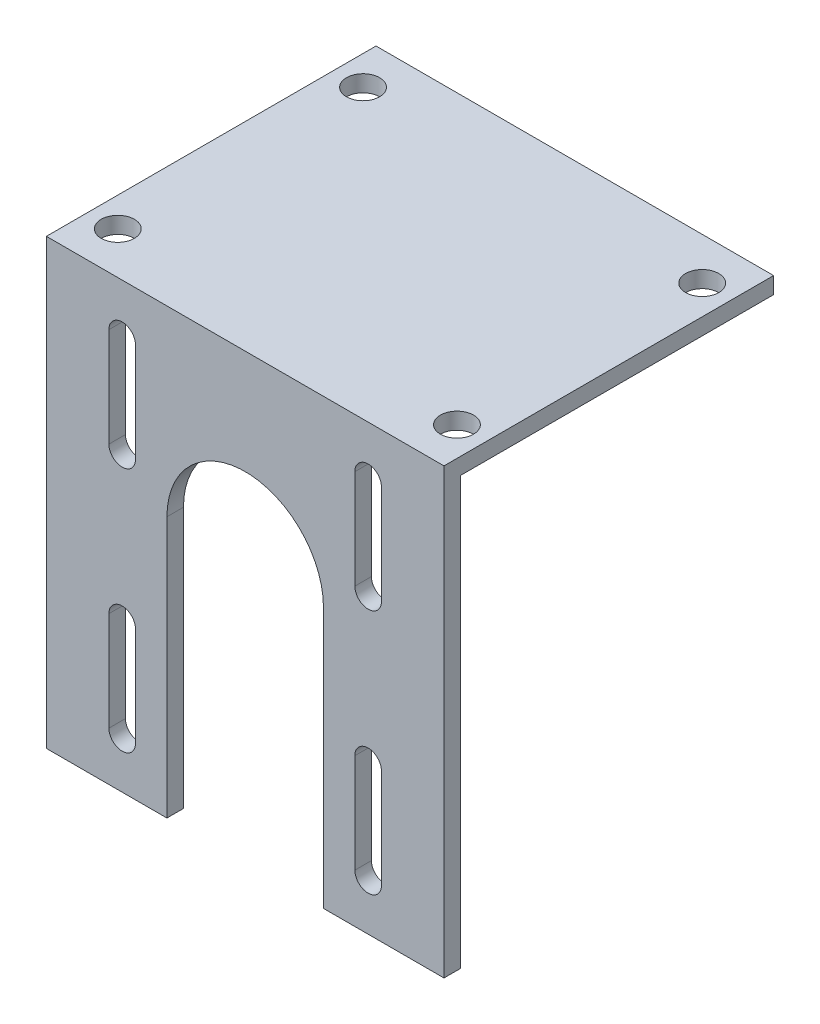
SolidWorks part; units mm, degrees
material "6061 Alloy"
ref_plane "Front Plane" through (0, 0, 0) normal (0, 0, 1) x (1, 0, 0)
ref_plane "Top Plane" through (0, 0, 0) normal (0, 1, 0) x (1, 0, 0)
ref_plane "Right Plane" through (0, 0, 0) normal (1, 0, 0) x (0, 0, -1)
sketch "Sketch1" plane through (0, 0, 0) normal (0, 0, 1) x (1, 0, 0)
  line L2 (0, 0) -> (0, -100)
  line L3 (0, -100) -> (76.2, -100)
  line L9 (76.2, -100) -> (76.2, 0)
  line L10 (0, 0) -> (76.2, 0)
  line L11 (14.53, -19) -> (61.67, -19) construction
  line L12 (38.1, 0) -> (38.1, -100) construction
  line L14 (14.53, -9.5) -> (14.53, -28.5) construction
  line L15 (61.67, -47.5975) -> (61.67, -19) construction
  line L16 (17.08, -9.5) -> (17.08, -28.5)
  line L17 (11.98, -9.5) -> (11.98, -28.5)
  line L18 (61.67, -9.5) -> (61.67, -28.5) construction
  line L19 (59.12, -9.5) -> (59.12, -28.5)
  line L20 (64.22, -9.5) -> (64.22, -28.5)
  line L21 (14.53, -75.64) -> (14.53, -56.64) construction
  line L22 (17.08, -75.64) -> (17.08, -56.64)
  line L23 (11.98, -75.64) -> (11.98, -56.64)
  line L24 (61.67, -75.64) -> (61.67, -56.64) construction
  line L25 (59.12, -75.64) -> (59.12, -56.64)
  line L26 (64.22, -75.64) -> (64.22, -56.64)
  arc A8 (17.08, -9.5) -> (11.98, -9.5) centre (14.53, -9.5) ccw
  arc A9 (11.98, -28.5) -> (17.08, -28.5) centre (14.53, -28.5) ccw
  arc A10 (59.12, -9.5) -> (64.22, -9.5) centre (61.67, -9.5) cw
  arc A11 (64.22, -28.5) -> (59.12, -28.5) centre (61.67, -28.5) cw
  arc A12 (17.08, -75.64) -> (11.98, -75.64) centre (14.53, -75.64) cw
  arc A13 (11.98, -56.64) -> (17.08, -56.64) centre (14.53, -56.64) cw
  arc A14 (59.12, -75.64) -> (64.22, -75.64) centre (61.67, -75.64) ccw
  arc A15 (64.22, -56.64) -> (59.12, -56.64) centre (61.67, -56.64) ccw
  point P10 (16.7578, -17.7303)
  point P11 (0, 0)
  point P12 (63.57, -68.5233)
  point P14 (0, 0)
  point P15 (0, 0)
  point P16 (38.1, -19)
  point P20 (14.53, -19)
  point P21 (76.2, -100)
  point P26 (0, 0)
  point P29 (76.2, 0)
  point P31 (61.67, -19)
  point P37 (14.53, -66.14)
  point P44 (61.67, -66.14)
  dimension "D3" = 47.14
  dimension "D4" = 47.14
  dimension "D6" = 19
  dimension "D5" = 2.55
  dimension "D1" = 76.2
  dimension "D2" = 100
  dimension "D7" = 19
  dimension "D8" = 19
  dimension "D9" = 19
extrude "Boss-Extrude1" add sketch "Sketch1" along normal blind 3.175
sketch "Sketch2" plane through (0, 0, 3.175) normal (0, 0, 1) x (1, 0, 0)
  line L0 (23.1, -35) -> (23.1, -100)
  line L1 (0, -100) -> (76.2, -100) construction
  line L2 (53.1, -35) -> (53.1, -100)
  line L3 (76.2, 0) -> (0, 0) construction
  line L8 (23.1, -100) -> (53.1, -100)
  arc A3 (23.1, -35) -> (53.1, -35) centre (38.1, -35) cw
  point P4 (38.1, 0)
  dimension "D1" = 15
  dimension "D2" = 35
extrude "Cut-Extrude2" cut sketch "Sketch2" against normal up to next
sketch "Sketch4" plane through (0, 0, 0) normal (0, 0, -1) x (-1, 0, 0)
  line L0 (0, 0) -> (0, -100) construction
  line L1 (-76.2, 0) -> (0, 0)
  line L2 (-76.2, 0) -> (-76.2, -3.175)
  line L3 (-76.2, -3.175) -> (0, -3.175)
  line L4 (0, 0) -> (0, -3.175)
  dimension "D1" = 3.175
extrude "Boss-Extrude2" add sketch "Sketch4" along normal blind 60
sketch "Sketch5" plane through (0, 0, 0) normal (0, 1, 0) x (1, 0, 0)
  line L2 (5.6, 51.9125) -> (70.6, 51.9125) construction
  line L3 (70.6, 51.9125) -> (70.6, 4.9125) construction
  line L4 (70.6, 4.9125) -> (5.6, 4.9125) construction
  line L5 (5.6, 4.9125) -> (5.6, 51.9125) construction
  line L6 (38.1, -940) -> (38.1, 49060) construction
  line L7 (0, 60) -> (76.2, 60) construction
  line L8 (-1000, 28.4125) -> (49000, 28.4125) construction
  line L9 (0, -3.175) -> (0, 60) construction
  circle A0 centre (5.6, 51.9125) radius 3.175
  circle A1 centre (5.6, 4.9125) radius 3.175
  circle A2 centre (70.6, 51.9125) radius 3.175
  circle A3 centre (70.6, 4.9125) radius 3.175
  point P13 (38.1, 60)
  point P14 (38.1, 51.9125)
  point P18 (0, 28.4125)
  point P19 (5.6, 28.4125)
  dimension "D1" = 6.35
  dimension "D2" = 65
  dimension "D3" = 47
extrude "Cut-Extrude3" cut sketch "Sketch5" against normal up to surface (3.175 mm away) up to face at (38.1, -3.175, -30)
sketch "Sketch6" plane through (0, 0, 3.175) normal (0, 0, 1) x (1, 0, 0)
  line L5 (0, 0) -> (0, -100) construction
  line L6 (0, -85) -> (76.2, -85)
  line L7 (0, -85) -> (0, -100)
  line L8 (0, -100) -> (76.2, -100)
  line L9 (76.2, -85) -> (76.2, -100)
  dimension "D1" = 15
extrude "Cut-Extrude4" cut sketch "Sketch6" against normal through all
